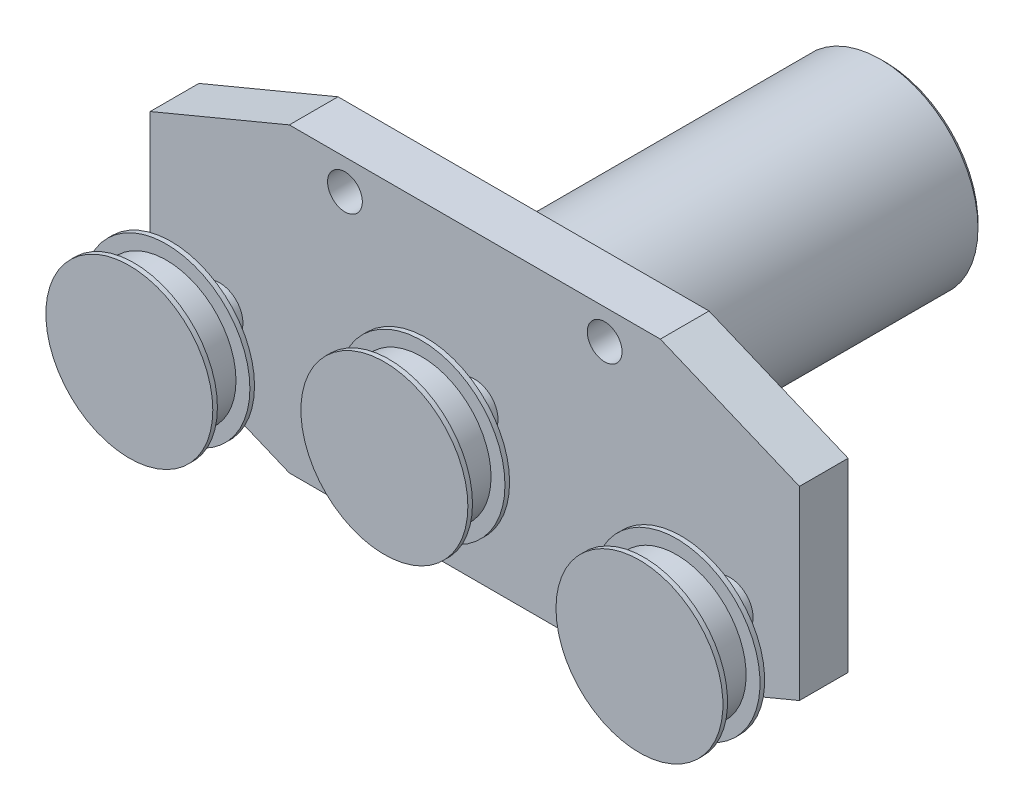
SolidWorks part; units mm, degrees
ref_plane "Front Plane" through (0, 0, 0) normal (0, 0, 1) x (1, 0, 0)
ref_plane "Top Plane" through (0, 0, 0) normal (0, 1, 0) x (1, 0, 0)
ref_plane "Right Plane" through (0, 0, 0) normal (1, 0, 0) x (0, 0, -1)
sketch "Sketch1" plane through (0, 0, 0) normal (0, 0, 1) x (1, 0, 0)
  line L0 (-20, 32.5) -> (-50, 20)
  line L1 (-20, 32.5) -> (20, 32.5)
  line L2 (-20, 32.5) -> (-20, -32.5)
  line L3 (-20, -32.5) -> (20, -32.5)
  line L4 (20, 32.5) -> (20, -32.5)
  line L5 (-20, 32.5) -> (20, -32.5) construction
  line L6 (-20, -32.5) -> (20, 32.5) construction
  line L7 (-50, 20) -> (-20, 20)
  line L8 (-50, 20) -> (-50, -20)
  line L9 (-50, -20) -> (-20, -20)
  line L10 (-20, 20) -> (-20, -20)
  line L11 (-50, 20) -> (-20, -20) construction
  line L12 (-50, -20) -> (-20, 20) construction
  line L13 (-50, -20) -> (-20, -32.5)
  line L14 (59.4, 0) -> (-59.4, 0) construction
  circle A0 centre (-8, 26) radius 2.25
  circle A1 centre (-8, -26) radius 2.25
  point P0 (0, 0)
  point P6 (-35, 0)
  dimension "D5" = 4.5
  dimension "D1" = 70
  dimension "D2" = 65
  dimension "D3" = 28
  dimension "D4" = 26
  dimension "D6" = 40
  dimension "D7" = 40
extrude "Boss-Extrude1" add sketch "Sketch1" along normal blind 10.5 contours L9 L13 L2 | L8 L9 L2 L7 | L0 L7 L2 | L4 L1 L2 L3 A0 A1 region at (-30, 24.1667, 0) region at (0.0991, 0, 0) region at (-35, 0, 0) region at (-30, -24.1667, 0)
mirror "Mirror1" about plane through (20, 0, 10.5) normal (1, 0, 0) of "Boss-Extrude1"
sketch "Sketch3" plane through (0, 0, 10.5) normal (0, 0, 1) x (1, 0, 0)
  line L0 (20, 32.5) -> (20, -32.5) construction
  line L1 (-20, 32.5) -> (60, 32.5) construction
  line L2 (-20, -32.5) -> (60, -32.5) construction
  line L4 (75, -9.5) -> (-35, -9.5) construction
  circle A0 centre (20, 0) radius 5
  circle A1 centre (-35, -9.5) radius 5
  circle A2 centre (75, -9.5) radius 5
  circle A3 centre (-35, -9.5) radius 18 construction
  circle A4 centre (75, -9.5) radius 18 construction
  dimension "D1" = 10
  dimension "D2" = 36
  dimension "D3" = 9.5
  dimension "D4" = 110
extrude "Boss-Extrude2" add sketch "Sketch3" along normal blind 10.5
sketch "Sketch4" plane through (0, 0, 10.5) normal (0, 0, 1) x (1, 0, 0)
  line L0 (59.4, 0) -> (-59.4, 0) construction
  line L1 (20, 32.5) -> (20, -31.5094) construction
  line L2 (-20, 32.5) -> (60, 32.5) construction
  circle A0 centre (-8, -26) radius 3.75
  circle A1 centre (-8, 26) radius 3.75
  circle A2 centre (48, 26) radius 3.75
  circle A3 centre (48, -26) radius 3.75
  dimension "D1" = 7.5
extrude "Cut-Extrude1" cut sketch "Sketch4" against normal blind 6
sketch "Sketch5" plane through (0, 0, 21) normal (0, 0, 1) x (1, 0, 0)
  circle A0 centre (20, 0) radius 18
  circle A1 centre (-35, -9.5) radius 18
  dimension "D1" = 36
extrude "Boss-Extrude3" add sketch "Sketch5" along normal blind 9
ref_plane "Plane1" through (0, 0, 29) normal (0, 0, 1) x (1, 0, 0)
sketch "Sketch7" plane through (0, 0, 29) normal (0, 0, 1) x (1, 0, 0)
  line L1 (-118.6146, 40.418) -> (48.6146, 40.418)
  line L2 (-118.6146, 40.418) -> (-118.6146, -59.418)
  line L3 (-118.6146, -59.418) -> (48.6146, -59.418)
  line L4 (48.6146, 40.418) -> (48.6146, -59.418)
  line L5 (-118.6146, 40.418) -> (48.6146, -59.418) construction
  line L6 (-118.6146, -59.418) -> (48.6146, 40.418) construction
  circle A0 centre (-35, -9.5) radius 15
  circle A1 centre (20, 0) radius 15
  dimension "D1" = 30
extrude "Cut-Extrude2" cut sketch "Sketch7" against normal blind 7
ref_plane "Plane2" through (20, 0, 0) normal (1, 0, 0) x (0, 0, -1)
mirror "Mirror2" about plane through (20, 0, 0) normal (1, 0, 0) of bodies 106
sketch "Sketch8" plane through (0, 0, 0) normal (0, 0, -1) x (-1, 0, 0)
  circle A0 centre (-20, 0) radius 21
  dimension "D1" = 42
extrude "Boss-Extrude4" add sketch "Sketch8" along normal blind 78
chamfer "Chamfer1" distance 1 angle 45 1 edges at (-1, 0, -78)
sketch "Sketch9" plane through (0, 0, 0) normal (0, 0, -1) x (-1, 0, 0)
  circle A0 centre (-75, -9.5) radius 2
  circle A1 centre (35, -9.5) radius 2
  dimension "D1" = 4
extrude "Boss-Extrude5" add sketch "Sketch9" along normal mid plane 6
